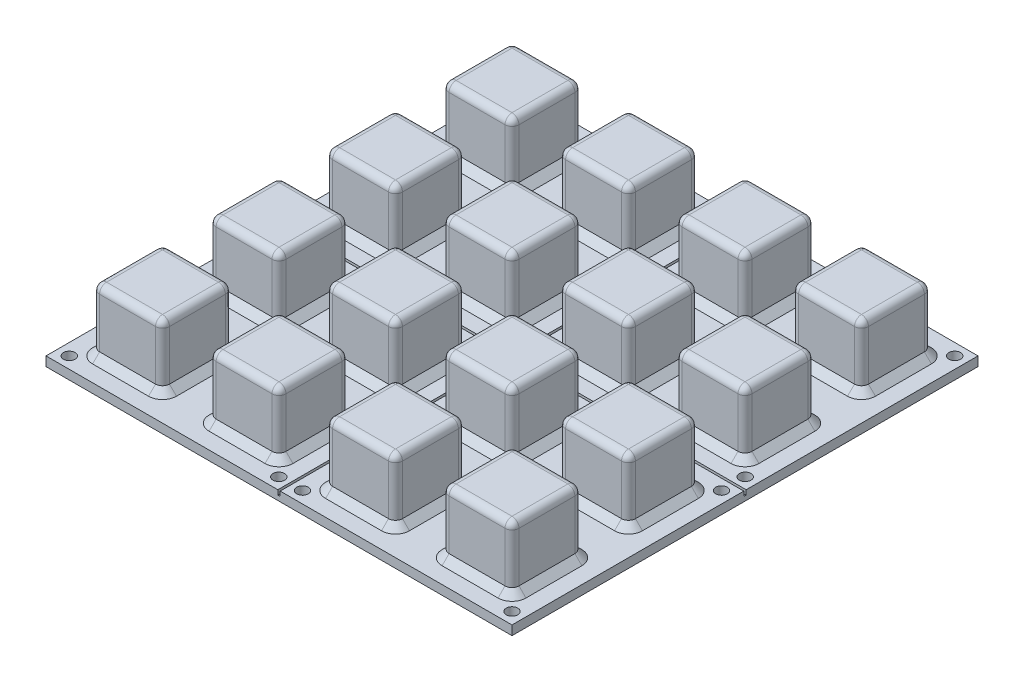
SolidWorks part; units mm, degrees
ref_plane "Front Plane" through (0, 0, 0) normal (0, 0, 1) x (1, 0, 0)
ref_plane "Top Plane" through (0, 0, 0) normal (0, 1, 0) x (1, 0, 0)
ref_plane "Right Plane" through (0, 0, 0) normal (1, 0, 0) x (0, 0, -1)
sketch "Sketch1" plane through (0, 0, 0) normal (0, 1, 0) x (1, 0, 0)
  line L0 (-18.5, -30) -> (-6.5, -30)
  line L1 (-20, -31.5) -> (-20, -43.5)
  line L2 (-18.5, -45) -> (-6.5, -45)
  line L3 (-5, -31.5) -> (-5, -43.5)
  line L4 (6.5, -30) -> (18.5, -30)
  line L5 (-43.5, -30) -> (-31.5, -30)
  line L6 (-45, -31.5) -> (-45, -43.5)
  line L7 (-43.5, -45) -> (-31.5, -45)
  line L8 (-30, -31.5) -> (-30, -43.5)
  line L9 (5, -31.5) -> (5, -43.5)
  line L10 (6.5, -45) -> (18.5, -45)
  line L11 (20, -31.5) -> (20, -43.5)
  line L12 (31.5, -30) -> (43.5, -30)
  line L13 (30, -31.5) -> (30, -43.5)
  line L14 (31.5, -45) -> (43.5, -45)
  line L15 (45, -31.5) -> (45, -43.5)
  line L16 (-18.5, -5) -> (-6.5, -5)
  line L17 (-20, -6.5) -> (-20, -18.5)
  line L18 (-18.5, -20) -> (-6.5, -20)
  line L19 (-5, -6.5) -> (-5, -18.5)
  line L20 (6.5, -5) -> (18.5, -5)
  line L21 (5, -6.5) -> (5, -18.5)
  line L22 (6.5, -20) -> (18.5, -20)
  line L23 (20, -6.5) -> (20, -18.5)
  line L24 (31.5, -5) -> (43.5, -5)
  line L25 (30, -6.5) -> (30, -18.5)
  line L26 (31.5, -20) -> (43.5, -20)
  line L27 (45, -6.5) -> (45, -18.5)
  line L28 (-18.5, 20) -> (-6.5, 20)
  line L29 (-20, 18.5) -> (-20, 6.5)
  line L30 (-18.5, 5) -> (-6.5, 5)
  line L31 (-5, 18.5) -> (-5, 6.5)
  line L32 (6.5, 20) -> (18.5, 20)
  line L33 (5, 18.5) -> (5, 6.5)
  line L34 (6.5, 5) -> (18.5, 5)
  line L35 (20, 18.5) -> (20, 6.5)
  line L36 (31.5, 20) -> (43.5, 20)
  line L37 (30, 18.5) -> (30, 6.5)
  line L38 (31.5, 5) -> (43.5, 5)
  line L39 (45, 18.5) -> (45, 6.5)
  line L40 (-18.5, 45) -> (-6.5, 45)
  line L41 (-20, 43.5) -> (-20, 31.5)
  line L42 (-18.5, 30) -> (-6.5, 30)
  line L43 (-5, 43.5) -> (-5, 31.5)
  line L44 (6.5, 45) -> (18.5, 45)
  line L45 (5, 43.5) -> (5, 31.5)
  line L46 (6.5, 30) -> (18.5, 30)
  line L47 (20, 43.5) -> (20, 31.5)
  line L48 (31.5, 45) -> (43.5, 45)
  line L49 (30, 43.5) -> (30, 31.5)
  line L50 (31.5, 30) -> (43.5, 30)
  line L51 (45, 43.5) -> (45, 31.5)
  line L52 (-43.5, -5) -> (-31.5, -5)
  line L53 (-45, -6.5) -> (-45, -18.5)
  line L54 (-43.5, -20) -> (-31.5, -20)
  line L55 (-30, -6.5) -> (-30, -18.5)
  line L56 (-43.5, 20) -> (-31.5, 20)
  line L57 (-45, 18.5) -> (-45, 6.5)
  line L58 (-43.5, 5) -> (-31.5, 5)
  line L59 (-30, 18.5) -> (-30, 6.5)
  line L60 (-43.5, 45) -> (-31.5, 45)
  line L61 (-45, 43.5) -> (-45, 31.5)
  line L62 (-43.5, 30) -> (-31.5, 30)
  line L63 (-30, 43.5) -> (-30, 31.5)
  arc A0 (-31.5, -30) -> (-30, -31.5) centre (-31.5, -31.5) cw
  arc A1 (-30, -43.5) -> (-31.5, -45) centre (-31.5, -43.5) cw
  arc A2 (-43.5, -45) -> (-45, -43.5) centre (-43.5, -43.5) cw
  arc A3 (-45, -31.5) -> (-43.5, -30) centre (-43.5, -31.5) cw
  arc A4 (-6.5, -30) -> (-5, -31.5) centre (-6.5, -31.5) cw
  arc A5 (-5, -43.5) -> (-6.5, -45) centre (-6.5, -43.5) cw
  arc A6 (-18.5, -45) -> (-20, -43.5) centre (-18.5, -43.5) cw
  arc A7 (-20, -31.5) -> (-18.5, -30) centre (-18.5, -31.5) cw
  arc A8 (18.5, -30) -> (20, -31.5) centre (18.5, -31.5) cw
  arc A9 (20, -43.5) -> (18.5, -45) centre (18.5, -43.5) cw
  arc A10 (6.5, -45) -> (5, -43.5) centre (6.5, -43.5) cw
  arc A11 (5, -31.5) -> (6.5, -30) centre (6.5, -31.5) cw
  arc A12 (43.5, -30) -> (45, -31.5) centre (43.5, -31.5) cw
  arc A13 (45, -43.5) -> (43.5, -45) centre (43.5, -43.5) cw
  arc A14 (31.5, -45) -> (30, -43.5) centre (31.5, -43.5) cw
  arc A15 (30, -31.5) -> (31.5, -30) centre (31.5, -31.5) cw
  arc A16 (-6.5, -5) -> (-5, -6.5) centre (-6.5, -6.5) cw
  arc A17 (-5, -18.5) -> (-6.5, -20) centre (-6.5, -18.5) cw
  arc A18 (-18.5, -20) -> (-20, -18.5) centre (-18.5, -18.5) cw
  arc A19 (-20, -6.5) -> (-18.5, -5) centre (-18.5, -6.5) cw
  arc A20 (18.5, -5) -> (20, -6.5) centre (18.5, -6.5) cw
  arc A21 (20, -18.5) -> (18.5, -20) centre (18.5, -18.5) cw
  arc A22 (6.5, -20) -> (5, -18.5) centre (6.5, -18.5) cw
  arc A23 (5, -6.5) -> (6.5, -5) centre (6.5, -6.5) cw
  arc A24 (43.5, -5) -> (45, -6.5) centre (43.5, -6.5) cw
  arc A25 (45, -18.5) -> (43.5, -20) centre (43.5, -18.5) cw
  arc A26 (31.5, -20) -> (30, -18.5) centre (31.5, -18.5) cw
  arc A27 (30, -6.5) -> (31.5, -5) centre (31.5, -6.5) cw
  arc A28 (-6.5, 20) -> (-5, 18.5) centre (-6.5, 18.5) cw
  arc A29 (-5, 6.5) -> (-6.5, 5) centre (-6.5, 6.5) cw
  arc A30 (-18.5, 5) -> (-20, 6.5) centre (-18.5, 6.5) cw
  arc A31 (-20, 18.5) -> (-18.5, 20) centre (-18.5, 18.5) cw
  arc A32 (18.5, 20) -> (20, 18.5) centre (18.5, 18.5) cw
  arc A33 (20, 6.5) -> (18.5, 5) centre (18.5, 6.5) cw
  arc A34 (6.5, 5) -> (5, 6.5) centre (6.5, 6.5) cw
  arc A35 (5, 18.5) -> (6.5, 20) centre (6.5, 18.5) cw
  arc A36 (43.5, 20) -> (45, 18.5) centre (43.5, 18.5) cw
  arc A37 (45, 6.5) -> (43.5, 5) centre (43.5, 6.5) cw
  arc A38 (31.5, 5) -> (30, 6.5) centre (31.5, 6.5) cw
  arc A39 (30, 18.5) -> (31.5, 20) centre (31.5, 18.5) cw
  arc A40 (-6.5, 45) -> (-5, 43.5) centre (-6.5, 43.5) cw
  arc A41 (-5, 31.5) -> (-6.5, 30) centre (-6.5, 31.5) cw
  arc A42 (-18.5, 30) -> (-20, 31.5) centre (-18.5, 31.5) cw
  arc A43 (-20, 43.5) -> (-18.5, 45) centre (-18.5, 43.5) cw
  arc A44 (18.5, 45) -> (20, 43.5) centre (18.5, 43.5) cw
  arc A45 (20, 31.5) -> (18.5, 30) centre (18.5, 31.5) cw
  arc A46 (6.5, 30) -> (5, 31.5) centre (6.5, 31.5) cw
  arc A47 (5, 43.5) -> (6.5, 45) centre (6.5, 43.5) cw
  arc A48 (43.5, 45) -> (45, 43.5) centre (43.5, 43.5) cw
  arc A49 (45, 31.5) -> (43.5, 30) centre (43.5, 31.5) cw
  arc A50 (31.5, 30) -> (30, 31.5) centre (31.5, 31.5) cw
  arc A51 (30, 43.5) -> (31.5, 45) centre (31.5, 43.5) cw
  arc A52 (-31.5, -5) -> (-30, -6.5) centre (-31.5, -6.5) cw
  arc A53 (-30, -18.5) -> (-31.5, -20) centre (-31.5, -18.5) cw
  arc A54 (-43.5, -20) -> (-45, -18.5) centre (-43.5, -18.5) cw
  arc A55 (-45, -6.5) -> (-43.5, -5) centre (-43.5, -6.5) cw
  arc A56 (-31.5, 20) -> (-30, 18.5) centre (-31.5, 18.5) cw
  arc A57 (-30, 6.5) -> (-31.5, 5) centre (-31.5, 6.5) cw
  arc A58 (-43.5, 5) -> (-45, 6.5) centre (-43.5, 6.5) cw
  arc A59 (-45, 18.5) -> (-43.5, 20) centre (-43.5, 18.5) cw
  arc A60 (-31.5, 45) -> (-30, 43.5) centre (-31.5, 43.5) cw
  arc A61 (-30, 31.5) -> (-31.5, 30) centre (-31.5, 31.5) cw
  arc A62 (-43.5, 30) -> (-45, 31.5) centre (-43.5, 31.5) cw
  arc A63 (-45, 43.5) -> (-43.5, 45) centre (-43.5, 43.5) cw
  point P2 (-30, -30)
  point P11 (-45, -45)
  point P14 (-45, -30)
  dimension "D2" = 1.5
  dimension "D1" = 15
  dimension "D3" = 15
  dimension "D5" = 30
  dimension "D6" = 30
  dimension "D4" = 4
extrude "Boss-Extrude1" add sketch "Sketch1" along normal blind 15.7
sketch "Sketch4" plane through (0, 0, 0) normal (0, 1, 0) x (1, 0, 0)
  line L1 (50, -50) -> (-50, -50)
  line L2 (50, -50) -> (50, 50)
  line L3 (50, 50) -> (-50, 50)
  line L4 (-50, -50) -> (-50, 50)
  point P0 (0, 0)
  dimension "D1" = 100
  dimension "D2" = 100
extrude "Boss-Extrude2" add sketch "Sketch4" along normal blind 2
sketch "Sketch5" plane through (0, 2, 0) normal (0, 1, 0) x (1, 0, 0)
  line L0 (50, 50) -> (-50, 50) construction
  line L1 (-0.25, -50) -> (0.25, -50)
  line L2 (-0.25, -50) -> (-0.25, 50)
  line L3 (-0.25, 50) -> (0.25, 50)
  line L4 (0.25, -50) -> (0.25, 50)
  line L5 (-0.25, -50) -> (0.25, 50) construction
  line L6 (-0.25, 50) -> (0.25, -50) construction
  line L7 (-50, 50) -> (-50, -50) construction
  line L8 (50, 0.25) -> (-50, 0.25)
  line L9 (50, 0.25) -> (50, -0.25)
  line L10 (50, -0.25) -> (-50, -0.25)
  line L11 (-50, 0.25) -> (-50, -0.25)
  line L12 (50, 0.25) -> (-50, -0.25) construction
  line L13 (50, -0.25) -> (-50, 0.25) construction
  point P0 (0, 0)
  point P8 (0, 0)
  dimension "D1" = 0.5
  dimension "D2" = 0.5
extrude "Cut-Extrude1" cut sketch "Sketch5" against normal blind 1 contours L2 L3 L4 L1 | L8 L11 L10 L9
sketch "Sketch6" plane through (0, 0, 0) normal (0, 1, 0) x (1, 0, 0)
  line L0 (-0.25, 50) -> (-50, 50) construction
  line L1 (-50, 50) -> (-50, 0.25) construction
  line L2 (0, 0) -> (-17.535, 0) construction
  line L3 (0, 0) -> (0, 12.1819) construction
  circle A0 centre (-47.5, 47.5) radius 1.25
  circle A1 centre (-2.542, 47.5) radius 1.25
  circle A2 centre (-2.542, 2.542) radius 1.25
  circle A3 centre (-47.5, 2.542) radius 1.25
  circle A4 centre (47.5, 2.542) radius 1.25
  circle A5 centre (2.542, 2.542) radius 1.25
  circle A6 centre (2.542, 47.5) radius 1.25
  circle A7 centre (47.5, 47.5) radius 1.25
  circle A8 centre (47.5, -47.5) radius 1.25
  circle A9 centre (2.542, -47.5) radius 1.25
  circle A10 centre (2.542, -2.542) radius 1.25
  circle A11 centre (47.5, -2.542) radius 1.25
  circle A12 centre (-47.5, -2.542) radius 1.25
  circle A13 centre (-2.542, -2.542) radius 1.25
  circle A14 centre (-2.542, -47.5) radius 1.25
  circle A15 centre (-47.5, -47.5) radius 1.25
  dimension "D1" = 2.5
  dimension "D2" = 2.5
  dimension "D3" = 2.5
  dimension "D4" = 2
  dimension "D5" = 2
extrude "Cut-Extrude3" cut sketch "Sketch6" along normal blind 3.54
chamfer "Chamfer4" distance 1.5 angle 45 128 edges at (-45, 2, 37.5) (-44.5607, 2, 44.5607) (-44.5607, 2, 30.4393) (-37.5, 2, 45) (-37.5, 2, 30) (-30.4393, 2, 44.5607) (-30.4393, 2, 30.4393) (-30, 2, 37.5) (20, 2, 37.5) (19.5607, 2, 44.5607) (19.5607, 2, 30.4393) (12.5, 2, 45) (12.5, 2, 30) (5.4393, 2, 44.5607) (5.4393, 2, 30.4393) (5, 2, 37.5) (45, 2, 37.5) (44.5607, 2, 44.5607) (44.5607, 2, 30.4393) (37.5, 2, 45) (37.5, 2, 30) (30.4393, 2, 44.5607) (30.4393, 2, 30.4393) (30, 2, 37.5) (45, 2, 12.5) (44.5607, 2, 19.5607) (44.5607, 2, 5.4393) (37.5, 2, 20) (37.5, 2, 5) (30.4393, 2, 19.5607) (30.4393, 2, 5.4393) (30, 2, 12.5) (20, 2, 12.5) (19.5607, 2, 19.5607) (19.5607, 2, 5.4393) (12.5, 2, 20) (12.5, 2, 5) (5.4393, 2, 19.5607) (5.4393, 2, 5.4393) (5, 2, 12.5) (20, 2, -12.5) (19.5607, 2, -5.4393) (19.5607, 2, -19.5607) (12.5, 2, -5) (12.5, 2, -20) (5.4393, 2, -5.4393) (5.4393, 2, -19.5607) (5, 2, -12.5) (45, 2, -12.5) (44.5607, 2, -5.4393) (44.5607, 2, -19.5607) (37.5, 2, -5) (37.5, 2, -20) (30.4393, 2, -5.4393) (30.4393, 2, -19.5607) (30, 2, -12.5) (45, 2, -37.5) (44.5607, 2, -30.4393) (44.5607, 2, -44.5607) (37.5, 2, -30) (37.5, 2, -45) (30.4393, 2, -30.4393) (30.4393, 2, -44.5607) (30, 2, -37.5) (20, 2, -37.5) (19.5607, 2, -30.4393) (19.5607, 2, -44.5607) (12.5, 2, -30) (12.5, 2, -45) (5.4393, 2, -30.4393) (5.4393, 2, -44.5607) (5, 2, -37.5) (-5, 2, -12.5) (-5.4393, 2, -5.4393) (-5.4393, 2, -19.5607) (-12.5, 2, -5) (-12.5, 2, -20) (-19.5607, 2, -5.4393) (-19.5607, 2, -19.5607) (-20, 2, -12.5) (-5, 2, -37.5) (-5.4393, 2, -30.4393) (-5.4393, 2, -44.5607) (-12.5, 2, -30) (-12.5, 2, -45) (-19.5607, 2, -30.4393) (-19.5607, 2, -44.5607) (-20, 2, -37.5) (-30, 2, -37.5) (-30.4393, 2, -30.4393) (-30.4393, 2, -44.5607) (-37.5, 2, -30) (-37.5, 2, -45) (-44.5607, 2, -30.4393) (-44.5607, 2, -44.5607) (-45, 2, -37.5) (-30, 2, -12.5) (-30.4393, 2, -5.4393) (-30.4393, 2, -19.5607) (-37.5, 2, -5) (-37.5, 2, -20) (-44.5607, 2, -5.4393) (-44.5607, 2, -19.5607) (-45, 2, -12.5) (-5, 2, 37.5) (-5.4393, 2, 44.5607) (-5.4393, 2, 30.4393) (-12.5, 2, 45) (-12.5, 2, 30) (-19.5607, 2, 44.5607) (-19.5607, 2, 30.4393) (-20, 2, 37.5) (-5, 2, 12.5) (-5.4393, 2, 19.5607) (-5.4393, 2, 5.4393) (-12.5, 2, 20) (-12.5, 2, 5) (-19.5607, 2, 19.5607) (-19.5607, 2, 5.4393) (-20, 2, 12.5) (-30, 2, 12.5) (-30.4393, 2, 19.5607) (-30.4393, 2, 5.4393) (-37.5, 2, 20) (-37.5, 2, 5) (-44.5607, 2, 19.5607) (-44.5607, 2, 5.4393) (-45, 2, 12.5)
fillet "Fillet2" radius 1.5 128 edges at (-44.5607, 15.7, 30.4393) (44.5607, 15.7, 30.4393) (37.5, 15.7, 30) (30.4393, 15.7, 30.4393) (30, 15.7, 37.5) (30.4393, 15.7, 44.5607) (37.5, 15.7, 45) (44.5607, 15.7, 44.5607) (45, 15.7, 37.5) (-45, 15.7, 37.5) (-5.4393, 15.7, 5.4393) (-12.5, 15.7, 5) (-19.5607, 15.7, 5.4393) (-20, 15.7, 12.5) (-19.5607, 15.7, 19.5607) (-12.5, 15.7, 20) (-5.4393, 15.7, 19.5607) (-5, 15.7, 12.5) (-44.5607, 15.7, 44.5607) (19.5607, 15.7, 5.4393) (12.5, 15.7, 5) (5.4393, 15.7, 5.4393) (5, 15.7, 12.5) (5.4393, 15.7, 19.5607) (12.5, 15.7, 20) (19.5607, 15.7, 19.5607) (20, 15.7, 12.5) (44.5607, 15.7, 5.4393) (37.5, 15.7, 5) (30.4393, 15.7, 5.4393) (30, 15.7, 12.5) (30.4393, 15.7, 19.5607) (37.5, 15.7, 20) (44.5607, 15.7, 19.5607) (45, 15.7, 12.5) (-37.5, 15.7, 45) (-5.4393, 15.7, -19.5607) (-12.5, 15.7, -20) (-19.5607, 15.7, -19.5607) (-20, 15.7, -12.5) (-19.5607, 15.7, -5.4393) (-12.5, 15.7, -5) (-5.4393, 15.7, -5.4393) (-5, 15.7, -12.5) (-30.4393, 15.7, 44.5607) (19.5607, 15.7, -19.5607) (12.5, 15.7, -20) (5.4393, 15.7, -19.5607) (5, 15.7, -12.5) (5.4393, 15.7, -5.4393) (12.5, 15.7, -5) (19.5607, 15.7, -5.4393) (20, 15.7, -12.5) (-30, 15.7, 37.5) (44.5607, 15.7, -19.5607) (37.5, 15.7, -20) (30.4393, 15.7, -19.5607) (30, 15.7, -12.5) (30.4393, 15.7, -5.4393) (37.5, 15.7, -5) (44.5607, 15.7, -5.4393) (45, 15.7, -12.5) (-5.4393, 15.7, -44.5607) (-12.5, 15.7, -45) (-19.5607, 15.7, -44.5607) (-20, 15.7, -37.5) (-19.5607, 15.7, -30.4393) (-12.5, 15.7, -30) (-5.4393, 15.7, -30.4393) (-5, 15.7, -37.5) (19.5607, 15.7, -44.5607) (12.5, 15.7, -45) (5.4393, 15.7, -44.5607) (5, 15.7, -37.5) (5.4393, 15.7, -30.4393) (12.5, 15.7, -30) (19.5607, 15.7, -30.4393) (20, 15.7, -37.5) (44.5607, 15.7, -44.5607) (37.5, 15.7, -45) (30.4393, 15.7, -44.5607) (30, 15.7, -37.5) (30.4393, 15.7, -30.4393) (37.5, 15.7, -30) (44.5607, 15.7, -30.4393) (45, 15.7, -37.5) (-30.4393, 15.7, 5.4393) (-37.5, 15.7, 5) (-44.5607, 15.7, 5.4393) (-45, 15.7, 12.5) (-44.5607, 15.7, 19.5607) (-37.5, 15.7, 20) (-30.4393, 15.7, 19.5607) (-30, 15.7, 12.5) (-30.4393, 15.7, -19.5607) (-37.5, 15.7, -20) (-44.5607, 15.7, -19.5607) (-45, 15.7, -12.5) (-44.5607, 15.7, -5.4393) (-37.5, 15.7, -5) (-30.4393, 15.7, -5.4393) (-30, 15.7, -12.5) (-30.4393, 15.7, 30.4393) (-30.4393, 15.7, -44.5607) (-37.5, 15.7, -45) (-44.5607, 15.7, -44.5607) (-45, 15.7, -37.5) (-44.5607, 15.7, -30.4393) (-37.5, 15.7, -30) (-30.4393, 15.7, -30.4393) (-30, 15.7, -37.5) (-5.4393, 15.7, 30.4393) (-12.5, 15.7, 30) (-19.5607, 15.7, 30.4393) (-20, 15.7, 37.5) (-19.5607, 15.7, 44.5607) (-12.5, 15.7, 45) (-5.4393, 15.7, 44.5607) (-5, 15.7, 37.5) (-37.5, 15.7, 30) (19.5607, 15.7, 30.4393) (12.5, 15.7, 30) (5.4393, 15.7, 30.4393) (5, 15.7, 37.5) (5.4393, 15.7, 44.5607) (12.5, 15.7, 45) (19.5607, 15.7, 44.5607) (20, 15.7, 37.5)
sketch "Sketch7" plane through (0, 0, 0) normal (0, -1, 0) x (1, 0, 0)
  line L0 (-50, 50) -> (50, 50) construction
  line L1 (-50, -50) -> (-50, 50) construction
  circle A0 centre (-37.5, 37.5) radius 4.25
  circle A1 centre (-12.5, 37.5) radius 4.25
  circle A2 centre (12.5, 37.5) radius 4.25
  circle A3 centre (37.5, 37.5) radius 4.25
  circle A4 centre (-12.5, 12.5) radius 4.25
  circle A5 centre (12.5, 12.5) radius 4.25
  circle A6 centre (37.5, 12.5) radius 4.25
  circle A7 centre (-12.5, -12.5) radius 4.25
  circle A8 centre (12.5, -12.5) radius 4.25
  circle A9 centre (37.5, -12.5) radius 4.25
  circle A10 centre (-12.5, -37.5) radius 4.25
  circle A11 centre (12.5, -37.5) radius 4.25
  circle A12 centre (37.5, -37.5) radius 4.25
  circle A13 centre (-37.5, 12.5) radius 4.25
  circle A14 centre (-37.5, -12.5) radius 4.25
  circle A15 centre (-37.5, -37.5) radius 4.25
  dimension "D5" = 8.5
  dimension "D1" = 12.5
  dimension "D2" = 12.5
  dimension "D3" = 4
extrude "Cut-Extrude4" cut sketch "Sketch7" against normal blind 12
fillet "Fillet3" radius 2.5 16 edges at (-37.5, 12, 33.25) (37.5, 12, 33.25) (37.5, 12, 8.25) (37.5, 12, -16.75) (37.5, 12, -41.75) (12.5, 12, -41.75) (12.5, 12, -16.75) (12.5, 12, 8.25) (12.5, 12, 33.25) (-12.5, 12, 33.25) (-12.5, 12, 8.25) (-12.5, 12, -16.75) (-12.5, 12, -41.75) (-37.5, 12, -41.75) (-37.5, 12, -16.75) (-37.5, 12, 8.25)
sketch "Sketch8" plane through (0, 0, 0) normal (0, -1, 0) x (1, 0, 0)
  line L0 (-18.4295, 29.5) -> (-6.5705, 29.5)
  line L1 (-43.4295, 29.5) -> (-31.5705, 29.5)
  line L2 (-45.5, 31.5705) -> (-45.5, 43.4295)
  line L3 (-43.4295, 45.5) -> (-31.5705, 45.5)
  line L4 (-29.5, 31.5705) -> (-29.5, 43.4295)
  line L5 (-45.5, 29.5) -> (-29.5, 45.5) construction
  line L6 (-45.5, 45.5) -> (-29.5, 29.5) construction
  line L7 (-20.5, 31.5705) -> (-20.5, 43.4295)
  line L8 (-18.4295, 45.5) -> (-6.5705, 45.5)
  line L9 (-4.5, 31.5705) -> (-4.5, 43.4295)
  line L10 (-20.5, 29.5) -> (-4.5, 45.5) construction
  line L11 (-20.5, 45.5) -> (-4.5, 29.5) construction
  line L12 (6.5705, 29.5) -> (18.4295, 29.5)
  line L13 (4.5, 31.5705) -> (4.5, 43.4295)
  line L14 (6.5705, 45.5) -> (18.4295, 45.5)
  line L15 (20.5, 31.5705) -> (20.5, 43.4295)
  line L16 (4.5, 29.5) -> (20.5, 45.5) construction
  line L17 (4.5, 45.5) -> (20.5, 29.5) construction
  line L18 (31.5705, 29.5) -> (43.4295, 29.5)
  line L19 (29.5, 31.5705) -> (29.5, 43.4295)
  line L20 (31.5705, 45.5) -> (43.4295, 45.5)
  line L21 (45.5, 31.5705) -> (45.5, 43.4295)
  line L22 (29.5, 29.5) -> (45.5, 45.5) construction
  line L23 (29.5, 45.5) -> (45.5, 29.5) construction
  line L24 (-18.4295, 4.5) -> (-6.5705, 4.5)
  line L25 (-20.5, 6.5705) -> (-20.5, 18.4295)
  line L26 (-18.4295, 20.5) -> (-6.5705, 20.5)
  line L27 (-4.5, 6.5705) -> (-4.5, 18.4295)
  line L28 (-20.5, 4.5) -> (-4.5, 20.5) construction
  line L29 (-20.5, 20.5) -> (-4.5, 4.5) construction
  line L30 (6.5705, 4.5) -> (18.4295, 4.5)
  line L31 (4.5, 6.5705) -> (4.5, 18.4295)
  line L32 (6.5705, 20.5) -> (18.4295, 20.5)
  line L33 (20.5, 6.5705) -> (20.5, 18.4295)
  line L34 (4.5, 4.5) -> (20.5, 20.5) construction
  line L35 (4.5, 20.5) -> (20.5, 4.5) construction
  line L36 (31.5705, 4.5) -> (43.4295, 4.5)
  line L37 (29.5, 6.5705) -> (29.5, 18.4295)
  line L38 (31.5705, 20.5) -> (43.4295, 20.5)
  line L39 (45.5, 6.5705) -> (45.5, 18.4295)
  line L40 (29.5, 4.5) -> (45.5, 20.5) construction
  line L41 (29.5, 20.5) -> (45.5, 4.5) construction
  line L42 (-18.4295, -20.5) -> (-6.5705, -20.5)
  line L43 (-20.5, -18.4295) -> (-20.5, -6.5705)
  line L44 (-18.4295, -4.5) -> (-6.5705, -4.5)
  line L45 (-4.5, -18.4295) -> (-4.5, -6.5705)
  line L46 (-20.5, -20.5) -> (-4.5, -4.5) construction
  line L47 (-20.5, -4.5) -> (-4.5, -20.5) construction
  line L48 (6.5705, -20.5) -> (18.4295, -20.5)
  line L49 (4.5, -18.4295) -> (4.5, -6.5705)
  line L50 (6.5705, -4.5) -> (18.4295, -4.5)
  line L51 (20.5, -18.4295) -> (20.5, -6.5705)
  line L52 (4.5, -20.5) -> (20.5, -4.5) construction
  line L53 (4.5, -4.5) -> (20.5, -20.5) construction
  line L54 (31.5705, -20.5) -> (43.4295, -20.5)
  line L55 (29.5, -18.4295) -> (29.5, -6.5705)
  line L56 (31.5705, -4.5) -> (43.4295, -4.5)
  line L57 (45.5, -18.4295) -> (45.5, -6.5705)
  line L58 (29.5, -20.5) -> (45.5, -4.5) construction
  line L59 (29.5, -4.5) -> (45.5, -20.5) construction
  line L60 (-18.4295, -45.5) -> (-6.5705, -45.5)
  line L61 (-20.5, -43.4295) -> (-20.5, -31.5705)
  line L62 (-18.4295, -29.5) -> (-6.5705, -29.5)
  line L63 (-4.5, -43.4295) -> (-4.5, -31.5705)
  line L64 (-20.5, -45.5) -> (-4.5, -29.5) construction
  line L65 (-20.5, -29.5) -> (-4.5, -45.5) construction
  line L66 (6.5705, -45.5) -> (18.4295, -45.5)
  line L67 (4.5, -43.4295) -> (4.5, -31.5705)
  line L68 (6.5705, -29.5) -> (18.4295, -29.5)
  line L69 (20.5, -43.4295) -> (20.5, -31.5705)
  line L70 (4.5, -45.5) -> (20.5, -29.5) construction
  line L71 (4.5, -29.5) -> (20.5, -45.5) construction
  line L72 (31.5705, -45.5) -> (43.4295, -45.5)
  line L73 (29.5, -43.4295) -> (29.5, -31.5705)
  line L74 (31.5705, -29.5) -> (43.4295, -29.5)
  line L75 (45.5, -43.4295) -> (45.5, -31.5705)
  line L76 (29.5, -45.5) -> (45.5, -29.5) construction
  line L77 (29.5, -29.5) -> (45.5, -45.5) construction
  line L78 (-43.4295, 4.5) -> (-31.5705, 4.5)
  line L79 (-45.5, 6.5705) -> (-45.5, 18.4295)
  line L80 (-43.4295, 20.5) -> (-31.5705, 20.5)
  line L81 (-29.5, 6.5705) -> (-29.5, 18.4295)
  line L82 (-45.5, 4.5) -> (-29.5, 20.5) construction
  line L83 (-45.5, 20.5) -> (-29.5, 4.5) construction
  line L84 (-43.4295, -20.5) -> (-31.5705, -20.5)
  line L85 (-45.5, -18.4295) -> (-45.5, -6.5705)
  line L86 (-43.4295, -4.5) -> (-31.5705, -4.5)
  line L87 (-29.5, -18.4295) -> (-29.5, -6.5705)
  line L88 (-45.5, -20.5) -> (-29.5, -4.5) construction
  line L89 (-45.5, -4.5) -> (-29.5, -20.5) construction
  line L90 (-43.4295, -45.5) -> (-31.5705, -45.5)
  line L91 (-45.5, -43.4295) -> (-45.5, -31.5705)
  line L92 (-43.4295, -29.5) -> (-31.5705, -29.5)
  line L93 (-29.5, -43.4295) -> (-29.5, -31.5705)
  line L94 (-45.5, -45.5) -> (-29.5, -29.5) construction
  line L95 (-45.5, -29.5) -> (-29.5, -45.5) construction
  arc A0 (-31.5705, 45.5) -> (-29.5, 43.4295) centre (-31.5705, 43.4295) cw
  arc A1 (-29.5, 31.5705) -> (-31.5705, 29.5) centre (-31.5705, 31.5705) cw
  arc A2 (-43.4295, 29.5) -> (-45.5, 31.5705) centre (-43.4295, 31.5705) cw
  arc A3 (-45.5, 43.4295) -> (-43.4295, 45.5) centre (-43.4295, 43.4295) cw
  arc A4 (-6.5705, 45.5) -> (-4.5, 43.4295) centre (-6.5705, 43.4295) cw
  arc A5 (-4.5, 31.5705) -> (-6.5705, 29.5) centre (-6.5705, 31.5705) cw
  arc A6 (-18.4295, 29.5) -> (-20.5, 31.5705) centre (-18.4295, 31.5705) cw
  arc A7 (-20.5, 43.4295) -> (-18.4295, 45.5) centre (-18.4295, 43.4295) cw
  arc A8 (18.4295, 45.5) -> (20.5, 43.4295) centre (18.4295, 43.4295) cw
  arc A9 (20.5, 31.5705) -> (18.4295, 29.5) centre (18.4295, 31.5705) cw
  arc A10 (6.5705, 29.5) -> (4.5, 31.5705) centre (6.5705, 31.5705) cw
  arc A11 (4.5, 43.4295) -> (6.5705, 45.5) centre (6.5705, 43.4295) cw
  arc A12 (43.4295, 45.5) -> (45.5, 43.4295) centre (43.4295, 43.4295) cw
  arc A13 (45.5, 31.5705) -> (43.4295, 29.5) centre (43.4295, 31.5705) cw
  arc A14 (31.5705, 29.5) -> (29.5, 31.5705) centre (31.5705, 31.5705) cw
  arc A15 (29.5, 43.4295) -> (31.5705, 45.5) centre (31.5705, 43.4295) cw
  arc A16 (-6.5705, 20.5) -> (-4.5, 18.4295) centre (-6.5705, 18.4295) cw
  arc A17 (-4.5, 6.5705) -> (-6.5705, 4.5) centre (-6.5705, 6.5705) cw
  arc A18 (-18.4295, 4.5) -> (-20.5, 6.5705) centre (-18.4295, 6.5705) cw
  arc A19 (-20.5, 18.4295) -> (-18.4295, 20.5) centre (-18.4295, 18.4295) cw
  arc A20 (18.4295, 20.5) -> (20.5, 18.4295) centre (18.4295, 18.4295) cw
  arc A21 (20.5, 6.5705) -> (18.4295, 4.5) centre (18.4295, 6.5705) cw
  arc A22 (6.5705, 4.5) -> (4.5, 6.5705) centre (6.5705, 6.5705) cw
  arc A23 (4.5, 18.4295) -> (6.5705, 20.5) centre (6.5705, 18.4295) cw
  arc A24 (43.4295, 20.5) -> (45.5, 18.4295) centre (43.4295, 18.4295) cw
  arc A25 (45.5, 6.5705) -> (43.4295, 4.5) centre (43.4295, 6.5705) cw
  arc A26 (31.5705, 4.5) -> (29.5, 6.5705) centre (31.5705, 6.5705) cw
  arc A27 (29.5, 18.4295) -> (31.5705, 20.5) centre (31.5705, 18.4295) cw
  arc A28 (-6.5705, -4.5) -> (-4.5, -6.5705) centre (-6.5705, -6.5705) cw
  arc A29 (-4.5, -18.4295) -> (-6.5705, -20.5) centre (-6.5705, -18.4295) cw
  arc A30 (-18.4295, -20.5) -> (-20.5, -18.4295) centre (-18.4295, -18.4295) cw
  arc A31 (-20.5, -6.5705) -> (-18.4295, -4.5) centre (-18.4295, -6.5705) cw
  arc A32 (18.4295, -4.5) -> (20.5, -6.5705) centre (18.4295, -6.5705) cw
  arc A33 (20.5, -18.4295) -> (18.4295, -20.5) centre (18.4295, -18.4295) cw
  arc A34 (6.5705, -20.5) -> (4.5, -18.4295) centre (6.5705, -18.4295) cw
  arc A35 (4.5, -6.5705) -> (6.5705, -4.5) centre (6.5705, -6.5705) cw
  arc A36 (43.4295, -4.5) -> (45.5, -6.5705) centre (43.4295, -6.5705) cw
  arc A37 (45.5, -18.4295) -> (43.4295, -20.5) centre (43.4295, -18.4295) cw
  arc A38 (31.5705, -20.5) -> (29.5, -18.4295) centre (31.5705, -18.4295) cw
  arc A39 (29.5, -6.5705) -> (31.5705, -4.5) centre (31.5705, -6.5705) cw
  arc A40 (-6.5705, -29.5) -> (-4.5, -31.5705) centre (-6.5705, -31.5705) cw
  arc A41 (-4.5, -43.4295) -> (-6.5705, -45.5) centre (-6.5705, -43.4295) cw
  arc A42 (-18.4295, -45.5) -> (-20.5, -43.4295) centre (-18.4295, -43.4295) cw
  arc A43 (-20.5, -31.5705) -> (-18.4295, -29.5) centre (-18.4295, -31.5705) cw
  arc A44 (18.4295, -29.5) -> (20.5, -31.5705) centre (18.4295, -31.5705) cw
  arc A45 (20.5, -43.4295) -> (18.4295, -45.5) centre (18.4295, -43.4295) cw
  arc A46 (6.5705, -45.5) -> (4.5, -43.4295) centre (6.5705, -43.4295) cw
  arc A47 (4.5, -31.5705) -> (6.5705, -29.5) centre (6.5705, -31.5705) cw
  arc A48 (43.4295, -29.5) -> (45.5, -31.5705) centre (43.4295, -31.5705) cw
  arc A49 (45.5, -43.4295) -> (43.4295, -45.5) centre (43.4295, -43.4295) cw
  arc A50 (31.5705, -45.5) -> (29.5, -43.4295) centre (31.5705, -43.4295) cw
  arc A51 (29.5, -31.5705) -> (31.5705, -29.5) centre (31.5705, -31.5705) cw
  arc A52 (-31.5705, 20.5) -> (-29.5, 18.4295) centre (-31.5705, 18.4295) cw
  arc A53 (-29.5, 6.5705) -> (-31.5705, 4.5) centre (-31.5705, 6.5705) cw
  arc A54 (-43.4295, 4.5) -> (-45.5, 6.5705) centre (-43.4295, 6.5705) cw
  arc A55 (-45.5, 18.4295) -> (-43.4295, 20.5) centre (-43.4295, 18.4295) cw
  arc A56 (-31.5705, -4.5) -> (-29.5, -6.5705) centre (-31.5705, -6.5705) cw
  arc A57 (-29.5, -18.4295) -> (-31.5705, -20.5) centre (-31.5705, -18.4295) cw
  arc A58 (-43.4295, -20.5) -> (-45.5, -18.4295) centre (-43.4295, -18.4295) cw
  arc A59 (-45.5, -6.5705) -> (-43.4295, -4.5) centre (-43.4295, -6.5705) cw
  arc A60 (-31.5705, -29.5) -> (-29.5, -31.5705) centre (-31.5705, -31.5705) cw
  arc A61 (-29.5, -43.4295) -> (-31.5705, -45.5) centre (-31.5705, -43.4295) cw
  arc A62 (-43.4295, -45.5) -> (-45.5, -43.4295) centre (-43.4295, -43.4295) cw
  arc A63 (-45.5, -31.5705) -> (-43.4295, -29.5) centre (-43.4295, -31.5705) cw
  point P0 (-37.5, 37.5)
  point P1 (-37.5, 37.5)
  point P21 (-12.5, 37.5)
  point P22 (-12.5, 37.5)
  point P39 (12.5, 37.5)
  point P40 (12.5, 37.5)
  point P57 (37.5, 37.5)
  point P58 (37.5, 37.5)
  point P75 (-12.5, 12.5)
  point P76 (-12.5, 12.5)
  point P93 (12.5, 12.5)
  point P94 (12.5, 12.5)
  point P111 (37.5, 12.5)
  point P112 (37.5, 12.5)
  point P129 (-12.5, -12.5)
  point P130 (-12.5, -12.5)
  point P147 (12.5, -12.5)
  point P148 (12.5, -12.5)
  point P165 (37.5, -12.5)
  point P166 (37.5, -12.5)
  point P183 (-12.5, -37.5)
  point P184 (-12.5, -37.5)
  point P201 (12.5, -37.5)
  point P202 (12.5, -37.5)
  point P219 (37.5, -37.5)
  point P220 (37.5, -37.5)
  point P237 (-37.5, 12.5)
  point P238 (-37.5, 12.5)
  point P255 (-37.5, -12.5)
  point P256 (-37.5, -12.5)
  point P273 (-37.5, -37.5)
  point P274 (-37.5, -37.5)
  dimension "D3" = 2.0705
  dimension "D1" = 16
  dimension "D2" = 16
  dimension "D4" = 4
extrude "Cut-Extrude6" cut sketch "Sketch8" against normal blind 2.5
sketch "Sketch9" plane through (0, 2.5, 0) normal (0, -1, 0) x (1, 0, 0)
  circle A0 centre (-37.5, 37.5) radius 5
  circle A1 centre (-37.5, 37.5) radius 7
  circle A2 centre (-12.5, 37.5) radius 5
  circle A3 centre (-12.5, 37.5) radius 7
  circle A4 centre (12.5, 37.5) radius 5
  circle A5 centre (12.5, 37.5) radius 7
  circle A6 centre (37.5, 37.5) radius 5
  circle A7 centre (37.5, 37.5) radius 7
  circle A8 centre (-12.5, 12.5) radius 5
  circle A9 centre (-12.5, 12.5) radius 7
  circle A10 centre (12.5, 12.5) radius 5
  circle A11 centre (12.5, 12.5) radius 7
  circle A12 centre (37.5, 12.5) radius 5
  circle A13 centre (37.5, 12.5) radius 7
  circle A14 centre (-12.5, -12.5) radius 5
  circle A15 centre (-12.5, -12.5) radius 7
  circle A16 centre (12.5, -12.5) radius 5
  circle A17 centre (12.5, -12.5) radius 7
  circle A18 centre (37.5, -12.5) radius 5
  circle A19 centre (37.5, -12.5) radius 7
  circle A20 centre (-12.5, -37.5) radius 5
  circle A21 centre (-12.5, -37.5) radius 7
  circle A22 centre (12.5, -37.5) radius 5
  circle A23 centre (12.5, -37.5) radius 7
  circle A24 centre (37.5, -37.5) radius 5
  circle A25 centre (37.5, -37.5) radius 7
  circle A26 centre (-37.5, 12.5) radius 5
  circle A27 centre (-37.5, 12.5) radius 7
  circle A28 centre (-37.5, -12.5) radius 5
  circle A29 centre (-37.5, -12.5) radius 7
  circle A30 centre (-37.5, -37.5) radius 5
  circle A31 centre (-37.5, -37.5) radius 7
  dimension "D1" = 10
  dimension "D2" = 14
  dimension "D3" = 4
extrude "Boss-Extrude3" add sketch "Sketch9" along normal blind 1 separate body
sketch "Sketch10" plane through (0, 2.5, 0) normal (0, -1, 0) x (1, 0, 0)
  circle A0 centre (-12.5, 37.5) radius 5
  circle A1 centre (-12.5, 37.5) radius 7
  circle A2 centre (-37.5, 37.5) radius 5 construction
  circle A3 centre (-37.5, 37.5) radius 7 construction
  circle A4 centre (12.5, 37.5) radius 5
  circle A5 centre (12.5, 37.5) radius 7
  circle A6 centre (37.5, 37.5) radius 5
  circle A7 centre (37.5, 37.5) radius 7
  circle A8 centre (-12.5, 12.5) radius 5
  circle A9 centre (-12.5, 12.5) radius 7
  circle A10 centre (12.5, 12.5) radius 5
  circle A11 centre (12.5, 12.5) radius 7
  circle A12 centre (37.5, 12.5) radius 5
  circle A13 centre (37.5, 12.5) radius 7
  circle A14 centre (-12.5, -12.5) radius 5
  circle A15 centre (-12.5, -12.5) radius 7
  circle A16 centre (12.5, -12.5) radius 5
  circle A17 centre (12.5, -12.5) radius 7
  circle A18 centre (37.5, -12.5) radius 5
  circle A19 centre (37.5, -12.5) radius 7
  circle A20 centre (-12.5, -37.5) radius 5
  circle A21 centre (-12.5, -37.5) radius 7
  circle A22 centre (12.5, -37.5) radius 5
  circle A23 centre (12.5, -37.5) radius 7
  circle A24 centre (37.5, -37.5) radius 5
  circle A25 centre (37.5, -37.5) radius 7
  circle A26 centre (-37.5, 12.5) radius 5
  circle A27 centre (-37.5, 12.5) radius 7
  circle A28 centre (-37.5, -12.5) radius 5
  circle A29 centre (-37.5, -12.5) radius 7
  circle A30 centre (-37.5, -37.5) radius 5
  circle A31 centre (-37.5, -37.5) radius 7
  circle A34 centre (-37.5, 37.5) radius 5
  circle A35 centre (-37.5, 37.5) radius 7
  dimension "D1" = 4
sketch "Sketch11" plane through (0, 0, 0) normal (0, -1, 0) x (1, 0, 0)
  line L0 (-37.5, 37.5) -> (-37.5, 12.5) construction
  line L1 (-37.5, 12.5) -> (-12.5, 12.5) construction
  line L2 (0, 0) -> (-15.4233, 0) construction
  line L3 (0, 0) -> (0, 16.4785) construction
  line L4 (-12.5, 12.5) -> (-12.5, 37.5) construction
  line L5 (-12.5, 37.5) -> (-37.5, 37.5) construction
  line L6 (37.935, 12.535) -> (37.935, 37.935) construction
  line L7 (12.535, 12.535) -> (37.935, 12.535) construction
  line L8 (12.535, 37.935) -> (12.535, 12.535) construction
  line L9 (37.935, 37.935) -> (12.535, 37.935) construction
  line L10 (37.935, -37.935) -> (12.535, -37.935) construction
  line L11 (12.535, -37.935) -> (12.535, -12.535) construction
  line L12 (12.535, -12.535) -> (37.935, -12.535) construction
  line L13 (37.935, -12.535) -> (37.935, -37.935) construction
  line L14 (-37.935, -12.535) -> (-37.935, -37.935) construction
  line L15 (-12.535, -12.535) -> (-37.935, -12.535) construction
  line L16 (-12.535, -37.935) -> (-12.535, -12.535) construction
  line L17 (-37.935, -37.935) -> (-12.535, -37.935) construction
  circle A0 centre (-25, 37.5) radius 1.25
  circle A1 centre (-37.5, 25) radius 1.25
  circle A2 centre (-12.5, 25) radius 1.25
  circle A3 centre (-25, 12.5) radius 1.25
  circle A4 centre (25, 12.5) radius 1.25
  circle A5 centre (12.5, 25) radius 1.25
  circle A6 centre (37.5, 25) radius 1.25
  circle A7 centre (25, 37.5) radius 1.25
  circle A8 centre (25, -37.5) radius 1.25
  circle A9 centre (37.5, -25) radius 1.25
  circle A10 centre (12.5, -25) radius 1.25
  circle A11 centre (25, -12.5) radius 1.25
  circle A12 centre (-25, -12.5) radius 1.25
  circle A13 centre (-12.5, -25) radius 1.25
  circle A14 centre (-37.5, -25) radius 1.25
  circle A15 centre (-25, -37.5) radius 1.25
  dimension "D1" = 2.5
  dimension "D2" = 2.5
extrude "Boss-Extrude6" add sketch "Sketch10" along normal blind 0.5 separate body
extrude "Boss-Extrude7" add sketch "Sketch11" along normal blind 1.5
chamfer "Chamfer6" distance 0.25 angle 45 16 edges at (-25, -1.5, -11.25) (-12.5, -1.5, -23.75) (-37.5, -1.5, -23.75) (-25, -1.5, -36.25) (25, -1.5, -38.75) (37.5, -1.5, -26.25) (12.5, -1.5, -26.25) (25, -1.5, -13.75) (25, -1.5, 13.75) (37.5, -1.5, 26.25) (25, -1.5, 38.75) (12.5, -1.5, 26.25) (-12.5, -1.5, 23.75) (-25, -1.5, 11.25) (-37.5, -1.5, 23.75) (-25, -1.5, 36.25)
